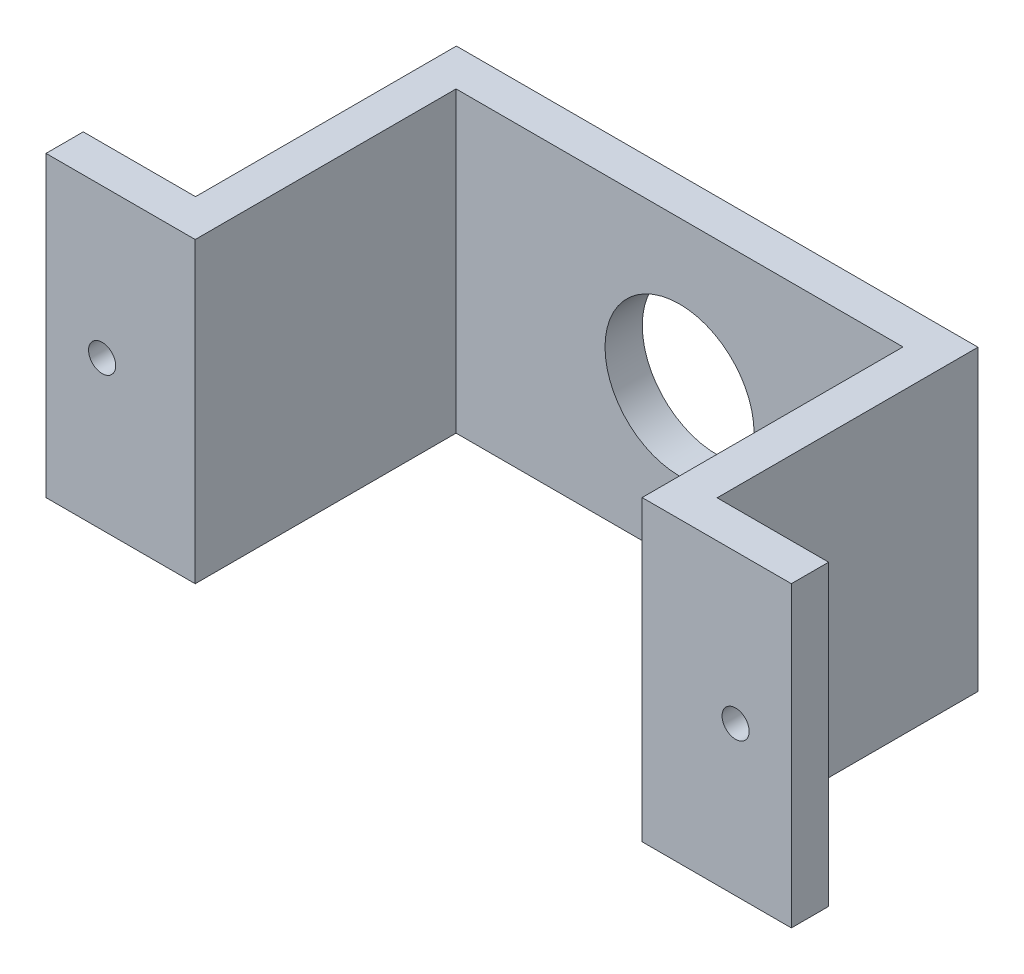
SolidWorks part; units mm, degrees
ref_plane "Front Plane" through (0, 0, 0) normal (0, 0, 1) x (1, 0, 0)
ref_plane "Top Plane" through (0, 0, 0) normal (0, 1, 0) x (1, 0, 0)
ref_plane "Right Plane" through (0, 0, 0) normal (1, 0, 0) x (0, 0, -1)
sketch "Sketch1" plane through (0, 0, 0) normal (0, 0, 1) x (1, 0, 0)
  line L1 (63.5, -25.4) -> (-63.5, -25.4)
  line L2 (63.5, -25.4) -> (63.5, 25.4)
  line L3 (63.5, 25.4) -> (-63.5, 25.4)
  line L4 (-63.5, -25.4) -> (-63.5, 25.4)
  line L5 (63.5, -25.4) -> (-63.5, 25.4) construction
  line L6 (63.5, 25.4) -> (-63.5, -25.4) construction
  point P0 (0, 0)
  dimension "D1" = 50.8
  dimension "D2" = 127
extrude "Boss-Extrude1" add sketch "Sketch1" along normal blind 50.8
sketch "Sketch2" plane through (0, 0, 0) normal (0, 0, -1) x (-1, 0, 0)
  line L0 (-63.5, 25.4) -> (-44.5039, 25.4)
  line L1 (-63.5, 25.4) -> (63.5, 25.4) construction
  line L2 (-44.5039, 25.4) -> (-44.5039, -25.4)
  line L3 (63.5, -25.4) -> (-63.5, -25.4) construction
  line L4 (-44.5039, -25.4) -> (-63.5, -25.4)
  line L5 (-63.5, -25.4) -> (-63.5, 25.4)
  line L6 (63.5, 25.4) -> (44.3726, 25.4)
  line L7 (44.3726, 25.4) -> (44.3726, -25.4)
  line L8 (44.3726, -25.4) -> (63.5, -25.4)
  line L9 (63.5, -25.4) -> (63.5, 25.4)
  dimension "D1" = 44.5039
  dimension "D2" = 44.3726
extrude "Cut-Extrude1" cut sketch "Sketch2" against normal blind 44.45
sketch "Sketch3" plane through (0, 0, 50.8) normal (0, 0, 1) x (1, 0, 0)
  line L0 (63.5, 25.4) -> (-63.5, 25.4) construction
  line L1 (38.0757, -25.4) -> (-38.0757, -25.4)
  line L2 (38.0757, -25.4) -> (38.0757, 25.4)
  line L3 (38.0757, 25.4) -> (-38.0757, 25.4)
  line L4 (-38.0757, -25.4) -> (-38.0757, 25.4)
  line L5 (38.0757, -25.4) -> (-38.0757, 25.4) construction
  line L6 (38.0757, 25.4) -> (-38.0757, -25.4) construction
  point P0 (0, 0)
  dimension "D1" = 76.1513
extrude "Cut-Extrude2" cut sketch "Sketch3" against normal blind 44.45
sketch "Sketch4" plane through (0, 0, 0) normal (0, 0, -1) x (-1, 0, 0)
  circle A0 centre (0, 0) radius 12.7
  dimension "D1" = 25.4
sketch "Sketch5" plane through (0, 0, 44.45) normal (0, 0, -1) x (-1, 0, 0)
  line L0 (0, 0) -> (-80.6006, 0) construction
  line L1 (-54.0019, 25.4) -> (-54.0019, -25.4) construction
  line L2 (-44.5039, 25.4) -> (-63.5, 25.4) construction
  line L3 (-63.5, -25.4) -> (-44.5039, -25.4) construction
  circle A0 centre (-54.0019, 0) radius 2.3114
  point P11 (-54.0019, 0)
  dimension "D1" = 4.6228
  dimension "D2" = 54.0019
sketch "Sketch6" plane through (0, 0, 44.45) normal (0, 0, -1) x (-1, 0, 0)
  line L0 (0, 0) -> (75.8811, 0) construction
  line L1 (53.9363, 25.4) -> (53.9363, -25.4) construction
  line L2 (63.5, 25.4) -> (44.3726, 25.4) construction
  line L3 (44.3726, -25.4) -> (63.5, -25.4) construction
  circle A0 centre (53.9363, 0) radius 2.3114
  dimension "D1" = 4.6228
extrude "Cut-Extrude3" cut sketch "Sketch4" against normal blind 44.45
extrude "Cut-Extrude4" cut sketch "Sketch5" against normal blind 44.45
extrude "Cut-Extrude5" cut sketch "Sketch6" against normal blind 44.45
